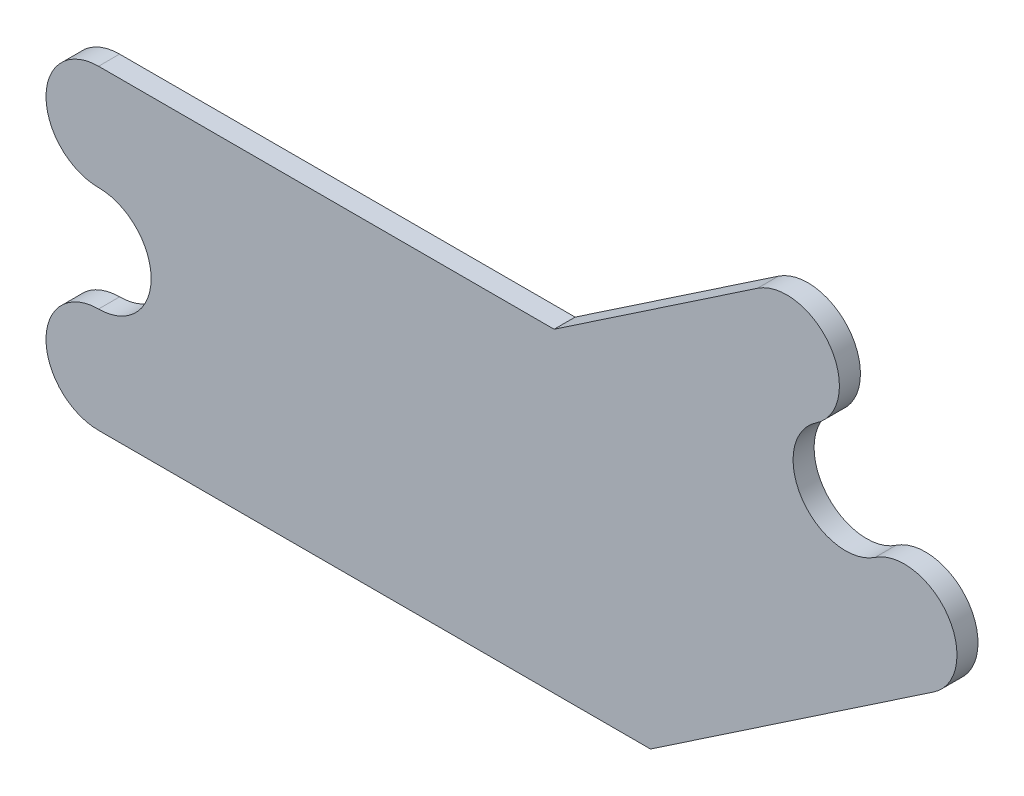
SolidWorks part; units mm, degrees
ref_plane "前视基准面" through (0, 0, 0) normal (0, 0, 1) x (1, 0, 0)
ref_plane "上视基准面" through (0, 0, 0) normal (0, 1, 0) x (1, 0, 0)
ref_plane "右视基准面" through (0, 0, 0) normal (1, 0, 0) x (0, 0, -1)
sketch "草图1" plane through (0, 0, 0) normal (0, 0, 1) x (1, 0, 0)
  line L0 (-19.9035, 9) -> (6.0965, 9) construction
  line L1 (0, 0) -> (-26, 0)
  line L2 (8.6867, 13.0033) -> (33.045, 29.4332) construction
  line L3 (0, 18) -> (-26, 18)
  line L4 (0, 18) -> (11.6065, 25.8287)
  line L5 (5.5032, 0) -> (21.672, 10.906)
  line L6 (19.9944, 13.3931) -> (16.6393, 18.3674) construction
  line L7 (0, 0) -> (5.5032, 0)
  line L8 (16.6393, 18.3674) -> (13.2841, 23.3416) construction
  line L9 (13.2841, 23.3416) -> (9.6186, 28.7759) construction
  arc A0 (-26, 6) -> (-26, 12) centre (-26, 9) ccw
  arc A1 (-26, 18) -> (-26, 12) centre (-26, 15) ccw
  arc A2 (-26, 6) -> (-26, 0) centre (-26, 3) ccw
  arc A3 (14.9617, 20.8545) -> (18.3168, 15.8802) centre (16.6393, 18.3674) ccw
  arc A4 (14.9617, 20.8545) -> (11.6065, 25.8287) centre (13.2841, 23.3416) ccw
  arc A5 (21.672, 10.906) -> (18.3168, 15.8802) centre (19.9944, 13.3931) ccw
  dimension "D2" = 6
  dimension "D5" = 3
  dimension "D1" = 18
  dimension "D3" = 26
  dimension "D4" = 18
  dimension "D6" = 14
  dimension "D7" = 146
sheet metal parameters "钣金1" thickness 1.2 parameters "D1"=2, "厚度"=1.2
base flange "基体-法兰1" sketch "草图1" thickness 1.2 reverse thickness direction no parameters "D1"=2
flat pattern "平板型式1" [suppressed]
sketch "折弯-线1" plane through (0, 0, 0) normal (0, 1, 0) x (1, 0, 0)
sketch3d "边界框1" [suppressed]
  line L0 (3, 3, 0) -> (-56.5735, 3, 0) construction
  line L1 (3, -15, 0) -> (-56.5735, -15, 0) construction
  line L2 (3, 3, 0) -> (3, -15, 0) construction
  line L3 (-56.5735, 3, 0) -> (-56.5735, -15, 0) construction
